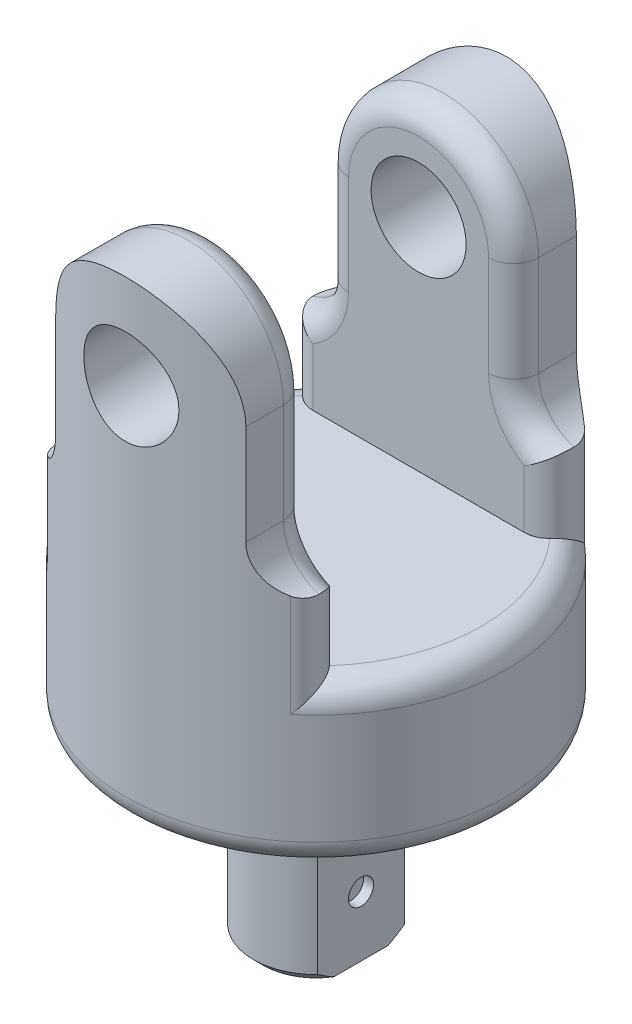
SolidWorks part; units mm, degrees
ref_plane "Front Plane" through (0, 0, 0) normal (0, 0, 1) x (1, 0, 0)
ref_plane "Top Plane" through (0, 0, 0) normal (0, 1, 0) x (1, 0, 0)
ref_plane "Right Plane" through (0, 0, 0) normal (1, 0, 0) x (0, 0, -1)
sketch "Sketch1" plane through (0, 0, 0) normal (0, 1, 0) x (1, 0, 0)
  circle A0 centre (0, 0) radius 19.05
  dimension "D1" = 38.1
extrude "Boss-Extrude1" add sketch "Sketch1" along normal blind 16
ref_plane "Plane1" through (0, 0, 10.25) normal (0, 0, 1) x (1, 0, 0)
sketch "Sketch2" plane through (0, 0, 10.25) normal (0, 0, 1) x (1, 0, 0)
  line L0 (-19.05, 0) -> (19.05, 0) construction
  line L1 (-9.5, 38) -> (-9.5, 28)
  line L2 (19.05, 16) -> (-19.05, 16) construction
  line L3 (9.5, 28) -> (9.5, 38)
  line L4 (-16.0574, 23.6073) -> (-16.0574, 16)
  line L5 (-16.0574, 16) -> (16.0574, 16)
  line L6 (16.0574, 16) -> (16.0574, 23.6073)
  arc A0 (9.5, 38) -> (-9.5, 38) centre (0, 38) ccw
  circle A1 centre (0, 38) radius 4.75
  arc A2 (-16.0574, 23.6073) -> (-9.5, 28) centre (-14.25, 28) ccw
  arc A3 (9.5, 28) -> (16.0574, 23.6073) centre (14.25, 28) ccw
  dimension "D1" = 9.5
  dimension "D2" = 9.5
  dimension "D4" = 9.5
  dimension "D5" = 9.5
  dimension "D3" = 38
  dimension "D6" = 12
extrude "Boss-Extrude2" add sketch "Sketch2" against normal up to surface and the other way up to surface contours A3 L3 A0 L1 A2 L4 L5 L6 A1 region at (0, 28.0478, 10.25) up to face at (0, 16, 19.05) other way up to face at (0, 16, 19.05)
sketch "Sketch3" plane through (0, 16, 0) normal (0, 1, 0) x (1, 0, 0)
  line L0 (-16.0574, 10.25) -> (-16.0574, -10.25) construction
  line L1 (-16.0574, 10.25) -> (16.0574, 10.25)
  line L2 (-16.0574, 10.25) -> (-16.0574, -10.25)
  line L3 (-16.0574, -10.25) -> (16.0574, -10.25)
  line L4 (16.0574, 10.25) -> (16.0574, -10.25)
  line L5 (16.0574, 10.25) -> (16.0574, -10.25) construction
  dimension "D1" = 20.5
  dimension "D2" = 10.25
extrude "Cut-Extrude2" cut sketch "Sketch3" along normal blind 31.5 contours L3 L4 L1 L2
fillet "Fillet1" radius 2.5 17 edges at (-11.6064, 24.0536, 10.25) (-9.5, 33, 10.25) (0, 47.5, 10.25) (9.5, 33, 10.25) (11.6064, 24.0536, -10.25) (9.5, 33, -10.25) (0, 47.5, -10.25) (-9.5, 33, -10.25) (0, 0, 19.05) (11.6064, 24.0536, 10.25) (-11.6064, 24.0536, -10.25)
sketch "Sketch4" plane through (0, 0, 0) normal (0, -1, 0) x (1, 0, 0)
  circle A0 centre (0, 0) radius 6.25
  dimension "D1" = 12.5
extrude "Boss-Extrude3" add sketch "Sketch4" along normal blind 19
chamfer "Chamfer1" distance 1 angle 45 1 edges at (0, -19, -6.25)
sketch "Sketch6" plane through (0, -19, 0) normal (0, -1, 0) x (1, 0, 0)
  line L0 (4.5, 4.3373) -> (4.5, -4.3373)
  arc A0 (4.5, -4.3373) -> (4.5, 4.3373) centre (0, 0) ccw
  circle A1 centre (0, 0) radius 6.25 construction
  dimension "D1" = 4.5
extrude "Cut-Extrude3" cut sketch "Sketch6" against normal blind 12.5
sketch "Sketch7" plane through (4.5, 0, 0) normal (1, 0, 0) x (0, 0, -1)
  circle A0 centre (0, -13) radius 1.25
  dimension "D1" = 2.5
  dimension "D2" = 13
extrude "Cut-Extrude4" cut sketch "Sketch7" against normal blind 1
